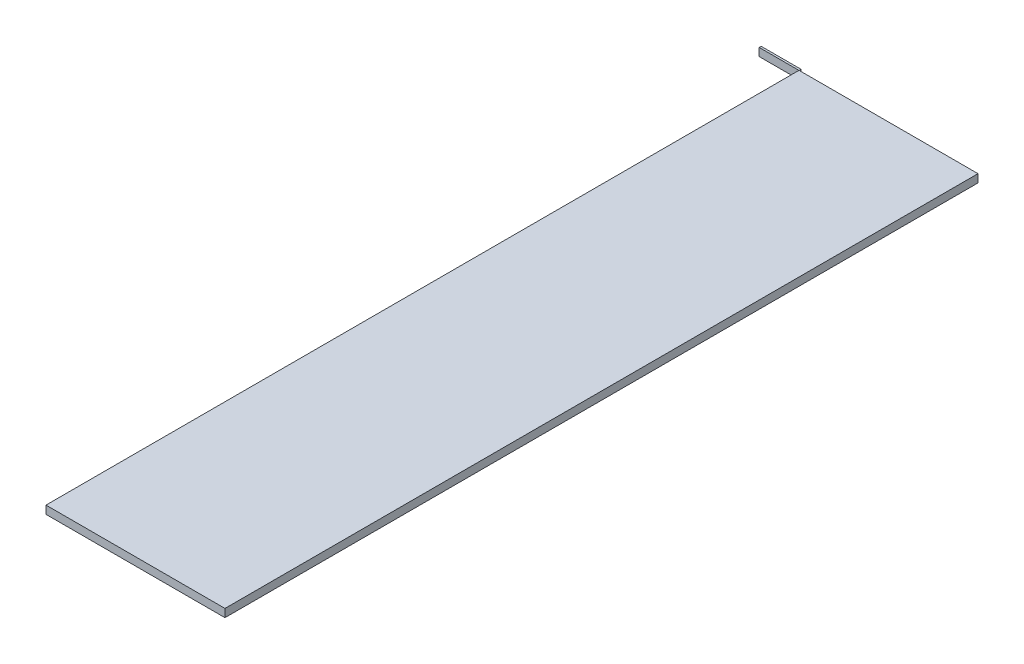
SolidWorks part; units mm, degrees
ref_plane "Front Plane" through (0, 0, 0) normal (0, 0, 1) x (1, 0, 0)
ref_plane "Top Plane" through (0, 0, 0) normal (0, 1, 0) x (1, 0, 0)
ref_plane "Right Plane" through (0, 0, 0) normal (1, 0, 0) x (0, 0, -1)
sketch "Sketch2" plane through (0, 0, 0) normal (0, 0, 1) x (1, 0, 0)
  line L1 (-47.8692, 21.2481) -> (206.1308, 21.2481)
  line L2 (-47.8692, 21.2481) -> (-47.8692, 8.5481)
  line L3 (-47.8692, 8.5481) -> (206.1308, 8.5481)
  line L4 (206.1308, 21.2481) -> (206.1308, 8.5481)
  dimension "D1" = 12.7
  dimension "D2" = 254
extrude "Boss-Extrude1" add sketch "Sketch2" along normal blind 50.8
sketch "Sketch3" plane through (0, 21.2481, 0) normal (0, 1, 0) x (1, 0, 0)
  circle A0 centre (79.1308, -28.4831) radius 17.1408
extrude "Boss-Extrude2" [suppressed] add sketch "Sketch3" along normal blind 19.05
sketch "Sketch4" [suppressed] plane through (0, 40.2981, 0) normal (0, 1, 0) x (1, 0, 0)
  line L1 (50.7675, -8.111) -> (126.0034, -8.111)
  line L2 (50.7675, -8.111) -> (50.7675, -48.0661)
  line L3 (50.7675, -48.0661) -> (126.0034, -48.0661)
  line L4 (126.0034, -8.111) -> (126.0034, -48.0661)
extrude "Boss-Extrude3" [suppressed] add sketch "Sketch4" along normal blind 38.1
scale "Scale2" scale about centroid uniform scaling yes scale factor 0.06
move or copy body "rotate" bodies to move or copy 105 copy no rotation origin (0, 33.6669, 26.5501) rotation axis (1, 0, 0) rotation angle 90
scale "Scale5" scale about centroid uniform scaling yes scale factor 0.25
move or copy body "-4 x" bodies to move or copy 111 copy no translate (-101.6, 0, 0)
move or copy body "-2 y" bodies to move or copy 117 copy no translate (0, -55.88, 0)
scale "Scale6" bodies to scale 121 scale about centroid uniform scaling yes scale factor 0.25
move or copy body "-2.1z" bodies to move or copy 122 copy no translate (0, 0, -30.48)
sketch "Sketch5" plane through (0, -21.1583, 0) normal (0, -1, 0) x (-1, 0, 0)
  line L1 (21.993, 22.675) -> (17.7087, 22.675)
  line L2 (21.993, 22.675) -> (21.993, 4.6477)
  line L3 (21.993, 4.6477) -> (17.7087, 4.6477)
  line L4 (17.7087, 22.675) -> (17.7087, 4.6477)
extrude "Boss-Extrude4" add sketch "Sketch5" against normal blind 0.1925
